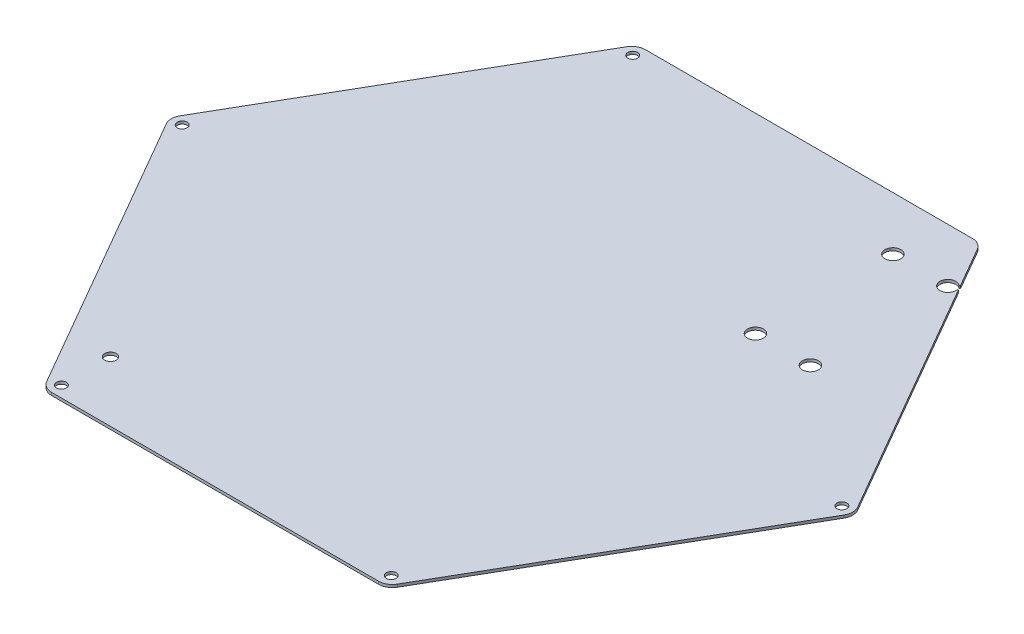
SolidWorks part; units mm, degrees
material "Thornel Mat VMA"
ref_plane "Front Plane" through (0, 0, 0) normal (0, 0, 1) x (1, 0, 0)
ref_plane "Top Plane" through (0, 0, 0) normal (0, 1, 0) x (1, 0, 0)
ref_plane "Right Plane" through (0, 0, 0) normal (1, 0, 0) x (0, 0, -1)
sketch "Sketch1" plane through (0, 0, 0) normal (0, 1, 0) x (1, 0, 0)
  line L1 (62.3538, 0) -> (187.0615, 0)
  line L2 (187.0615, 0) -> (249.4153, 108)
  line L3 (249.4153, 108) -> (187.0615, 216)
  line L4 (187.0615, 216) -> (62.3538, 216)
  line L5 (62.3538, 216) -> (0, 108)
  line L6 (0, 108) -> (62.3538, 0)
  circle A0 centre (124.7077, 108) radius 108 construction
  dimension "D1" = 216
extrude "Boss-Extrude1" add sketch "Sketch1" along normal blind 1
fillet "Fillet1" radius 5 6 edges at (0, 0.5, -108) (62.3538, 0.5, -216) (187.0615, 0.5, -216) (249.4153, 0.5, -108) (62.3538, 0.5, 0) (187.0615, 0.5, 0)
sketch "Sketch2" plane through (0, 1, 0) normal (0, 1, 0) x (1, 0, 0)
  line L0 (124.7077, 0) -> (124.7077, 216) construction
  line L1 (65.2406, 0) -> (184.1747, 0) construction
  line L2 (184.1747, 216) -> (65.2406, 216) construction
  line L3 (124.7077, 108) -> (244.7077, 108) construction
  line L4 (174.7077, 196.57) -> (194.7077, 196.57)
  line L5 (174.7077, 196.57) -> (174.7077, 146.57)
  line L6 (174.7077, 146.57) -> (194.7077, 146.57)
  line L7 (194.7077, 196.57) -> (194.7077, 146.57)
  line L8 (174.7077, 196.57) -> (194.7077, 146.57) construction
  line L9 (174.7077, 146.57) -> (194.7077, 196.57) construction
  line L10 (124.7077, 108) -> (64.7077, 211.923) construction
  line L11 (124.7077, 108) -> (4.7077, 108) construction
  line L12 (124.7077, 108) -> (64.7077, 4.077) construction
  line L13 (124.7077, 108) -> (184.7077, 4.077) construction
  point P6 (184.7077, 171.57)
  dimension "D1" = 50
  dimension "D2" = 20
  dimension "D3" = 50
  dimension "D4" = 38.57
  dimension "D5" = 120
  dimension "D6" = 60
  dimension "D7" = 60
hole_wizard "M5 Clearance Hole1" positions "Sketch4" profile "Sketch5" hole size "M5" standard "ANSI Metric"
sketch "Sketch4" plane through (0, 1, 0) normal (0, 1, 0) x (1, 0, 0)
  point P0 (174.7077, 146.57)
  point P3 (194.7077, 146.57)
  point P6 (194.7077, 196.57)
  point P9 (174.7077, 196.57)
sketch "Sketch5" plane through (174.7077, 1, -146.57) normal (1, 0, 0) x (0, 0, 1)
  line L0 (0, 0) -> (0, 6.7425)
  line L1 (0, 6.7425) -> (2.9, 5)
  line L2 (2.9, 5) -> (2.9, 0)
  line L5 (2.9, 0) -> (0, 0)
  line L10 (0, 6.7425) -> (-2.9, 5) construction
  line L11 (0, -6.35) -> (0, 107.95) construction
  dimension "Hole Dia." = 5.8
  dimension "Hole Depth" = 5
  dimension "Drill Angle" = 118
hole_wizard "M3 Clearance Hole1" positions "Sketch7" profile "Sketch8" hole size "M3" standard "ANSI Metric" end condition through all
sketch "Sketch7" plane through (0, 1, 0) normal (0, 1, 0) x (1, 0, 0)
  point P0 (4.7077, 108)
  point P3 (64.7077, 211.923)
  point P6 (244.7077, 108)
  point P9 (184.7077, 4.077)
  point P12 (64.7077, 4.077)
sketch "Sketch8" plane through (4.7077, 1, -108) normal (1, 0, 0) x (0, 0, 1)
  line L0 (0, 0) -> (0, 1)
  line L1 (0, 1) -> (1.8, 1)
  line L2 (1.8, 1) -> (1.8, 0)
  line L5 (1.8, 0) -> (0, 0)
  line L11 (0, -6.35) -> (0, 107.95) construction
  dimension "Thru Hole Dia." = 3.6
  dimension "Thru Hole Depth" = 1
sketch "Sketch9" plane through (0, 1, 0) normal (0, 1, 0) x (1, 0, 0)
  line L0 (196.564, 198.798) -> (196.8858, 198.9838)
  line L1 (247.9719, 110.5) -> (188.5049, 213.5) construction
  line L2 (197.5653, 197.0637) -> (197.8871, 197.2495)
  line L3 (196.8858, 198.9838) -> (197.8871, 197.2495)
  line L4 (196.564, 198.798) -> (197.5653, 197.0637)
  circle A0 centre (194.7077, 196.57) radius 2.9 construction
extrude "Cut-Extrude1" cut sketch "Sketch9" against normal through all
sketch "Sketch10" plane through (0, 1, 0) normal (0, 1, 0) x (1, 0, 0)
  line L0 (58.9342, 211.923) -> (64.7077, 211.923) construction
  line L1 (64.7077, 211.923) -> (64.7077, 21.923) construction
  line L2 (64.7077, 21.923) -> (48.6307, 21.923) construction
  line L3 (58.9342, 211.923) -> (4.7077, 118) construction
  line L4 (48.6307, 21.923) -> (4.7077, 98) construction
  line L5 (4.7077, 98) -> (4.7077, 118) construction
  line L7 (60.9105, 213.5) -> (1.4434, 110.5) construction
  line L8 (1.4434, 105.5) -> (60.9105, 2.5) construction
  circle A0 centre (4.7077, 108) radius 2.1 construction
  circle A1 centre (4.7077, 108) radius 1.8 construction
  circle A2 centre (64.7077, 211.923) radius 1.8 construction
  circle A3 centre (64.7077, 21.923) radius 2.1
  circle A4 centre (64.7077, 211.923) radius 2.1 construction
  dimension "D2" = 190
  dimension "D3" = 4.2
extrude "Cut-Extrude2" cut sketch "Sketch10" against normal through all
